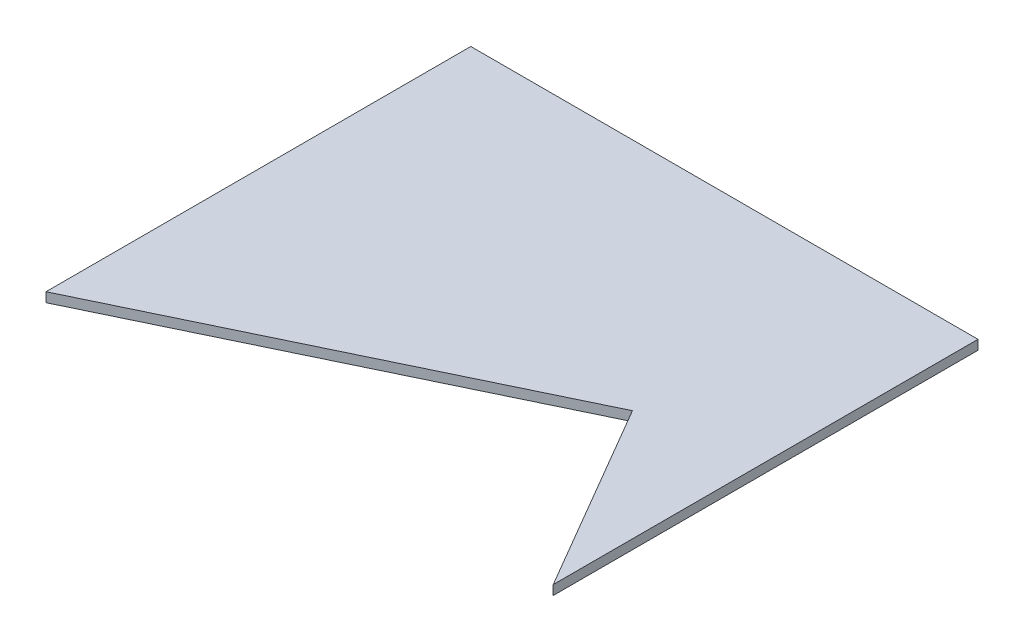
SolidWorks part; units mm, degrees
ref_plane "Front Plane" through (0, 0, 0) normal (0, 0, 1) x (1, 0, 0)
ref_plane "Top Plane" through (0, 0, 0) normal (0, 1, 0) x (1, 0, 0)
ref_plane "Right Plane" through (0, 0, 0) normal (1, 0, 0) x (0, 0, -1)
sketch "Sketch1" plane through (0, 0, 0) normal (0, 1, 0) x (1, 0, 0)
  line L0 (-80, -37) -> (-80, -97)
  line L1 (-80, -37) -> (80, -37)
  line L2 (-80, -37) -> (-80, 37)
  line L3 (-80, 37) -> (80, 37)
  line L4 (80, -37) -> (80, 37)
  line L5 (-80, -37) -> (80, 37) construction
  line L6 (-80, 37) -> (80, -37) construction
  line L7 (-80, -97) -> (45, -37)
  line L8 (45, -37) -> (80, -97)
  line L9 (80, -97) -> (80, -37)
  point P0 (0, 0)
  point P9 (0, 0)
  dimension "D1" = 160
  dimension "D2" = 74
  dimension "D3" = 35
  dimension "D4" = 60
extrude "Boss-Extrude1" add sketch "Sketch1" along normal blind 3 contours L0 L7 L1 | L1 L4 L3 L2 | L8 L9 L1 region at (-38.3333, 0, 57) region at (0, 0, 0) region at (68.3333, 0, 57)
